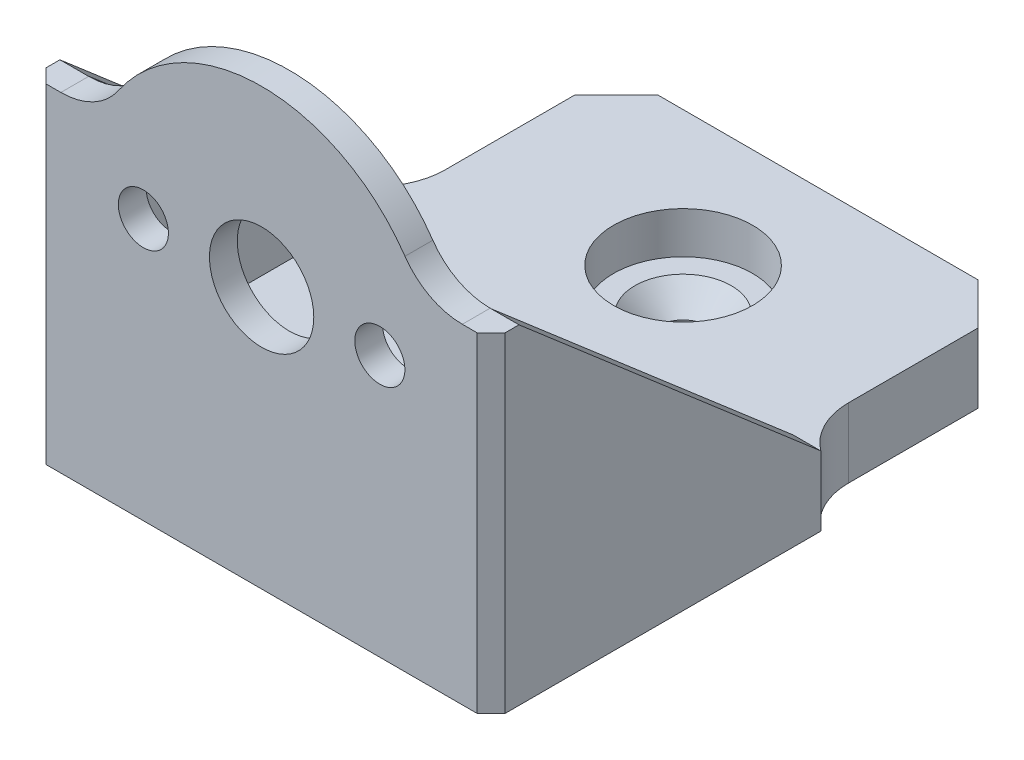
SolidWorks part; units mm, degrees
material "ABS"
ref_plane "Front Plane" through (0, 0, 0) normal (0, 0, 1) x (1, 0, 0)
ref_plane "Top Plane" through (0, 0, 0) normal (0, 1, 0) x (1, 0, 0)
ref_plane "Right Plane" through (0, 0, 0) normal (1, 0, 0) x (0, 0, -1)
sketch "Sketch1" plane through (0, 0, 0) normal (0, 1, 0) x (1, 0, 0)
  line L0 (0, 0) -> (0, 9.7) construction
  line L1 (-11.5, 9.7) -> (11.5, 9.7)
  line L2 (-11.5, 9.7) -> (-11.5, -30.3)
  line L3 (-11.5, -30.3) -> (11.5, -30.3)
  line L4 (11.5, 9.7) -> (11.5, -30.3)
  line L5 (0, 0) -> (0, -20) construction
  circle A0 centre (0, 0) radius 1.75
  circle A1 centre (0, -20) radius 1.75
  dimension "D1" = 3.5
  dimension "D2" = 20
  dimension "D3" = 40
  dimension "D4" = 23
  dimension "D5" = 9.7
extrude "Boss-Extrude1" add sketch "Sketch1" along normal blind 5
sketch "Sketch2" plane through (0, 5, 0) normal (0, 1, 0) x (1, 0, 0)
  line L0 (11.5, -30.3) -> (11.5, 9.7) construction
  line L1 (-11.5, -30.3) -> (11.5, -30.3)
  line L2 (-11.5, -30.3) -> (-11.5, -28.3)
  line L3 (-11.5, -28.3) -> (11.5, -28.3)
  line L4 (11.5, -30.3) -> (11.5, -28.3)
  dimension "D1" = 2
extrude "Boss-Extrude2" add sketch "Sketch2" along normal blind 50
sketch "Sketch3" plane through (0, 0, 30.3) normal (0, 0, 1) x (1, 0, 0)
  line L0 (-11.5, 0) -> (11.5, 0) construction
  line L1 (-11.5, 23.699) -> (-11.5, 55)
  line L3 (-11.5, 55) -> (11.5, 55)
  line L4 (-11.5, 55) -> (11.5, 55) construction
  line L13 (11.5, 55) -> (11.5, 23.699)
  circle A0 centre (0, 18.8) radius 8.5 construction
  circle A1 centre (-8.5, 18.8) radius 1.8
  circle A2 centre (8.5, 18.8) radius 1.8
  circle A3 centre (0, 18.8) radius 3.75
  arc A4 (11.5, 23.699) -> (-11.5, 23.699) centre (0, 18.8) ccw
  dimension "D1" = 17
  dimension "D2" = 3.6
  dimension "D3" = 7.5
  dimension "D5" = 25
  dimension "D4" = 18.8
extrude "Cut-Extrude1" cut sketch "Sketch3" against normal through all
sketch "Sketch4" plane through (-11.5, 0, 0) normal (-1, 0, 0) x (0, 0, 1)
  line L6 (30.3, 0) -> (30.3, 23.699)
  line L7 (30.3, 23.699) -> (28.3, 23.699)
  line L8 (28.3, 23.699) -> (28.3, 5)
  line L9 (28.3, 5) -> (-9.7, 5)
  line L10 (-9.7, 5) -> (-9.7, 0)
  line L11 (-9.7, 0) -> (30.3, 0)
  line L12 (30.3, 0) -> (30.3, 23.699)
  line L13 (30.3, 23.699) -> (28.3, 23.699)
  line L14 (28.3, 23.699) -> (28.3, 5)
  line L15 (28.3, 5) -> (-9.7, 5)
  line L16 (-9.7, 5) -> (-9.7, 0)
  line L17 (-9.7, 0) -> (30.3, 0)
  dimension "D1" = 0
extrude "Boss-Extrude3" add sketch "Sketch4" along normal blind 3
extrude "Boss-Extrude4" add sketch "Sketch4<2>" against normal blind 3 from surface starting at face at (11.5, 9.5663, 16.3)
sketch "Sketch4<2>" plane through (-11.5, 0, 0) normal (-1, 0, 0) x (0, 0, 1) same geometry as "Sketch4"
sketch "Sketch5" plane through (14.5, 0, 0) normal (1, 0, 0) x (0, 0, -1)
  line L0 (-30.3, 23.699) -> (-30.3, 0)
  line L1 (-30.3, 0) -> (-6.601, 0)
  line L2 (9.7, 0) -> (-30.3, 0) construction
  line L3 (-6.601, 0) -> (-6.601, 5)
  line L4 (-28.3, 5) -> (9.7, 5) construction
  line L5 (-6.601, 5) -> (-28.3, 23.699)
  line L6 (-28.3, 23.699) -> (-30.3, 23.699)
extrude "Boss-Extrude5" add sketch "Sketch5" along normal blind 2
extrude "Boss-Extrude6" add sketch "Sketch5<2>" against normal blind 2 from surface starting at face at (-14.5, 9.5663, 16.3)
sketch "Sketch5<2>" plane through (14.5, 0, 0) normal (1, 0, 0) x (0, 0, -1) same geometry as "Sketch5"
sketch "Sketch6" plane through (0, 5, 0) normal (0, 1, 0) x (1, 0, 0)
  circle A0 centre (0, 0) radius 5
  circle A1 centre (0, -20) radius 5
  dimension "D1" = 10
extrude "Cut-Extrude2" cut sketch "Sketch6" against normal blind 3
hole_wizard "CSK for M3 Hex Socket Countersunk Head Screw1" positions "Sketch7" profile "Sketch8" countersink size "M3" standard "DIN" end condition through all
sketch "Sketch7" plane through (0, 2, 0) normal (0, 1, 0) x (1, 0, 0)
  point P0 (0, 0)
  point P3 (0, -20)
sketch "Sketch8" plane through (0, 2, 0) normal (1, 0, 0) x (0, 0, 1)
  line L0 (0, 0) -> (0, 2)
  line L1 (0, 2) -> (1.8, 2)
  line L2 (1.8, 2) -> (1.8, 1.67)
  line L3 (1.8, 1.67) -> (3.47, 0)
  line L5 (3.47, 0) -> (0, 0)
  line L6 (-1.8, 1.67) -> (-3.47, 0) construction
  line L11 (0, -6.35) -> (0, 107.95) construction
  dimension "Thru Hole Dia." = 3.6
  dimension "Thru Hole Depth" = 2
  dimension "Near C'Sink Dia." = 6.94
  dimension "Near C'Sink Angle" = 90
chamfer "Chamfer1" distance 3 angle 45 2 edges at (14.5, 2.5, -9.7) (-14.5, 2.5, -9.7)
chamfer "Chamfer2" distance 1 angle 45 2 edges at (16.5, 11.8495, 30.3) (-16.5, 11.8495, 30.3)
fillet "Fillet1" radius 5 4 edges at (11.5, 23.699, 29.3) (-11.5, 23.699, 29.3) (-14.5, 2.5, 6.601) (14.5, 2.5, 6.601)
